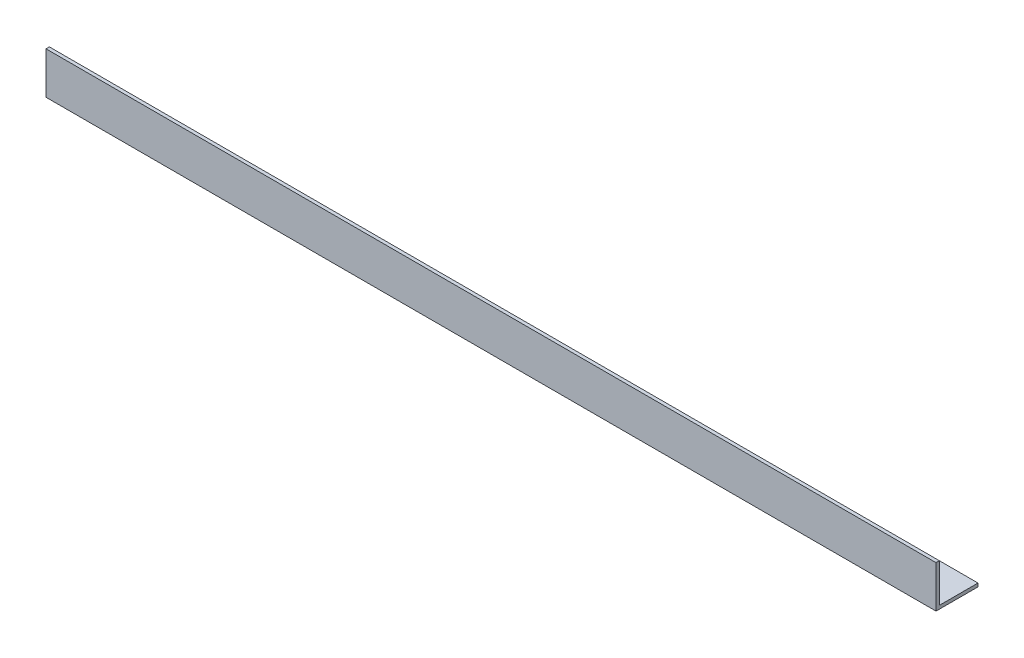
SolidWorks part; units mm, degrees
ref_plane "Спереди" through (0, 0, 0) normal (0, 0, 1) x (1, 0, 0)
ref_plane "Сверху" through (0, 0, 0) normal (0, 1, 0) x (1, 0, 0)
ref_plane "Справа" through (0, 0, 0) normal (1, 0, 0) x (0, 0, -1)
sketch "Эскиз1" plane through (0, 0, 0) normal (1, 0, 0) x (0, 0, -1)
  line L0 (0, 25) -> (0, 0)
  line L1 (0, 0) -> (25, 0)
extrude "Вытянуть-Тонкостенный1" add sketch "Эскиз1" along normal blind 530 thin thin type one direction reverse wall 2
